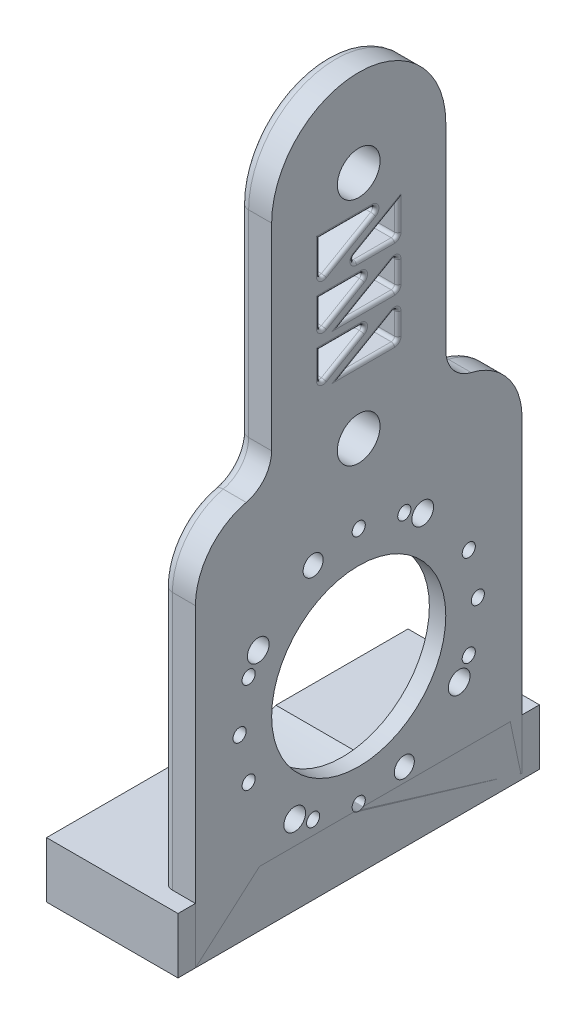
SolidWorks part; units mm, degrees
ref_plane "Front Plane" through (0, 0, 0) normal (0, 0, 1) x (1, 0, 0)
ref_plane "Top Plane" through (0, 0, 0) normal (0, 1, 0) x (1, 0, 0)
ref_plane "Right Plane" through (0, 0, 0) normal (1, 0, 0) x (0, 0, -1)
sketch "Sketch2" plane through (0, 0, 0) normal (1, 0, 0) x (0, 0, -1)
  line L0 (-49.7, 0) -> (-49.7, -54.7)
  line L1 (-49.7, -54.7) -> (49.7, -54.7)
  line L2 (49.7, -54.7) -> (49.7, 30)
  line L3 (0, 0) -> (0, 130) construction
  line L4 (-49.7, 0) -> (-49.7, 130)
  line L6 (49.7, 130) -> (49.7, 30)
  line L7 (-4.0065, 60) -> (3.9935, 60) construction
  line L8 (-49.7, 130) -> (49.7, 130) construction
  arc A0 (-32.0764, 15.2865) -> (-34.9048, 12.4581) centre (-33.4906, 13.8723) ccw
  arc A1 (-34.9048, 12.4581) -> (-32.0764, 15.2865) centre (-33.4906, 13.8723) ccw
  arc A74 (-20.5317, -3.7195) -> (-23.1344, -1.6907) centre (-21.8331, -2.7051) ccw
  arc A75 (-23.1344, -1.6907) -> (-20.5317, -3.7195) centre (-21.8331, -2.7051) ccw
  arc A76 (-16.2541, -14.2736) -> (-18.8568, -12.2448) centre (-17.5554, -13.2592) ccw
  arc A77 (-18.8568, -12.2448) -> (-16.2541, -14.2736) centre (-17.5554, -13.2592) ccw
  arc A78 (-7.2725, -21.275) -> (-9.8752, -19.2461) centre (-8.5738, -20.2605) ccw
  arc A79 (-9.8752, -19.2461) -> (-7.2725, -21.275) centre (-8.5738, -20.2605) ccw
  arc A80 (4.0065, -22.8475) -> (1.4038, -20.8186) centre (2.7051, -21.8331) ccw
  arc A81 (1.4038, -20.8186) -> (4.0065, -22.8475) centre (2.7051, -21.8331) ccw
  arc A82 (14.5606, -18.5698) -> (11.9579, -16.541) centre (13.2592, -17.5554) ccw
  arc A83 (11.9579, -16.541) -> (14.5606, -18.5698) centre (13.2592, -17.5554) ccw
  arc A84 (21.5619, -9.5882) -> (18.9592, -7.5594) centre (20.2605, -8.5738) ccw
  arc A85 (18.9592, -7.5594) -> (21.5619, -9.5882) centre (20.2605, -8.5738) ccw
  arc A86 (23.1344, 1.6907) -> (20.5317, 3.7195) centre (21.8331, 2.7051) ccw
  arc A87 (20.5317, 3.7195) -> (23.1344, 1.6907) centre (21.8331, 2.7051) ccw
  arc A88 (18.8568, 12.2448) -> (16.2541, 14.2736) centre (17.5554, 13.2592) ccw
  arc A89 (16.2541, 14.2736) -> (18.8568, 12.2448) centre (17.5554, 13.2592) ccw
  arc A90 (9.8752, 19.2461) -> (7.2725, 21.275) centre (8.5738, 20.2605) ccw
  arc A91 (7.2725, 21.275) -> (9.8752, 19.2461) centre (8.5738, 20.2605) ccw
  arc A92 (-1.4038, 20.8186) -> (-4.0065, 22.8475) centre (-2.7051, 21.8331) ccw
  arc A93 (-4.0065, 22.8475) -> (-1.4038, 20.8186) centre (-2.7051, 21.8331) ccw
  arc A94 (-11.9579, 16.541) -> (-14.5606, 18.5698) centre (-13.2592, 17.5554) ccw
  arc A95 (-14.5606, 18.5698) -> (-11.9579, 16.541) centre (-13.2592, 17.5554) ccw
  arc A96 (-18.9592, 7.5594) -> (-21.5619, 9.5882) centre (-20.2605, 8.5738) ccw
  arc A97 (-21.5619, 9.5882) -> (-18.9592, 7.5594) centre (-20.2605, 8.5738) ccw
  arc A98 (-17.1437, -28.2395) -> (-21.8106, -32.9064) centre (-19.4771, -30.5729) ccw
  arc A99 (-21.8106, -32.9064) -> (-17.1437, -28.2395) centre (-19.4771, -30.5729) ccw
  arc A102 (32.9064, -17.1437) -> (28.2395, -21.8106) centre (30.5729, -19.4771) ccw
  arc A103 (28.2395, -21.8106) -> (32.9064, -17.1437) centre (30.5729, -19.4771) ccw
  arc A104 (21.8106, 32.9064) -> (17.1437, 28.2395) centre (19.4771, 30.5729) ccw
  arc A105 (17.1437, 28.2395) -> (21.8106, 32.9064) centre (19.4771, 30.5729) ccw
  arc A108 (-28.2395, 21.8106) -> (-32.9064, 17.1437) centre (-30.5729, 19.4771) ccw
  arc A109 (-32.9064, 17.1437) -> (-28.2395, 21.8106) centre (-30.5729, 19.4771) ccw
  arc A110 (-20.9002, 16.2921) -> (20.9002, -16.2921) centre (0, 0) ccw
  arc A111 (20.9002, -16.2921) -> (-20.9002, 16.2921) centre (0, 0) ccw
  circle A112 centre (0, 0) radius 40.5
  arc A113 (16.029, -31.334) -> (11.7156, -35.6473) centre (13.8723, -33.4906) ccw
  arc A114 (-37.6642, -1.4142) -> (-34.8358, 1.4142) centre (-36.25, 0) ccw
  arc A115 (-34.8358, 1.4142) -> (-37.6642, -1.4142) centre (-36.25, 0) ccw
  arc A116 (-34.9048, -15.2865) -> (-32.0764, -12.4581) centre (-33.4906, -13.8723) ccw
  arc A117 (-32.0764, -12.4581) -> (-34.9048, -15.2865) centre (-33.4906, -13.8723) ccw
  arc A118 (-12.4581, -32.0764) -> (-15.2865, -34.9048) centre (-13.8723, -33.4906) ccw
  arc A119 (-15.2865, -34.9048) -> (-12.4581, -32.0764) centre (-13.8723, -33.4906) ccw
  arc A120 (-1.4142, -37.6642) -> (1.4142, -34.8358) centre (0, -36.25) ccw
  arc A121 (1.4142, -34.8358) -> (-1.4142, -37.6642) centre (0, -36.25) ccw
  arc A122 (32.0764, -15.2865) -> (34.9048, -12.4581) centre (33.4906, -13.8723) ccw
  arc A123 (34.9048, -12.4581) -> (32.0764, -15.2865) centre (33.4906, -13.8723) ccw
  arc A124 (34.8358, -1.4142) -> (37.6642, 1.4142) centre (36.25, 0) ccw
  arc A125 (37.6642, 1.4142) -> (34.8358, -1.4142) centre (36.25, 0) ccw
  arc A126 (32.0764, 12.4581) -> (34.9048, 15.2865) centre (33.4906, 13.8723) ccw
  arc A127 (34.9048, 15.2865) -> (32.0764, 12.4581) centre (33.4906, 13.8723) ccw
  arc A128 (15.2865, 34.9048) -> (12.4581, 32.0764) centre (13.8723, 33.4906) ccw
  arc A129 (12.4581, 32.0764) -> (15.2865, 34.9048) centre (13.8723, 33.4906) ccw
  arc A130 (-1.4142, 34.8358) -> (1.4142, 37.6642) centre (0, 36.25) ccw
  arc A131 (1.4142, 37.6642) -> (-1.4142, 34.8358) centre (0, 36.25) ccw
  arc A134 (11.7156, -35.6473) -> (16.029, -31.334) centre (13.8723, -33.4906) ccw
  arc A135 (-16.029, 31.334) -> (-11.7156, 35.6473) centre (-13.8723, 33.4906) ccw
  arc A136 (-11.7156, 35.6473) -> (-16.029, 31.334) centre (-13.8723, 33.4906) ccw
  arc A137 (49.7, 130) -> (-49.7, 130) centre (0, 130) ccw
  circle A138 centre (-0.0065, 60) radius 6.5
  circle A139 centre (0, 130) radius 6.5
  dimension "D1" = 130
  dimension "D2" = 54.7
  dimension "D3" = 70
extrude "Boss-Extrude1" add sketch "Sketch2" along normal blind 5 contours A112 A131 A130 A129 A128 A127 A126 A125 A124 A123 A122 A121 A120 A119 A118 A117 A116 A115 A114 A1 A0 A99 A98 A103 A102 A105 A104 A109 A108 A111 | L4 A112 region at (0, 74.4467, -0.0001) region at (0, 0, 39.3545)
extrude "Boss-Extrude2" add sketch "Sketch2<5>" against normal blind 5 contours L4 A112 region at (0, 74.4467, -0.0001)
sketch "Sketch2<5>" plane through (0, 0, 0) normal (1, 0, 0) x (0, 0, -1) same geometry as "Sketch2"
ref_plane "Plane1" through (0, -54.7, 0) normal (0, -1, 0) x (-1, 0, 0)
sketch "Sketch3" plane through (0, -54.7, 0) normal (0, -1, 0) x (-1, 0, 0)
  line L0 (-5, 0) -> (35, 0) construction
  line L1 (-5, 55) -> (35, 55)
  line L2 (-5, 55) -> (-5, -55)
  line L3 (-5, -55) -> (35, -55)
  line L5 (35, -55) -> (35, 0)
  line L6 (35, 55) -> (35, 0)
  dimension "D1" = 40
  dimension "D2" = 55
extrude "Boss-Extrude3" add sketch "Sketch3" against normal blind 17 separate body
sketch "Sketch7" plane through (5, 0, 0) normal (1, 0, 0) x (0, 0, -1)
  arc A0 (-32.0764, 15.2865) -> (-34.9048, 12.4581) centre (-33.4906, 13.8723) ccw
  arc A1 (-34.9048, 12.4581) -> (-32.0764, 15.2865) centre (-33.4906, 13.8723) ccw
  arc A2 (-20.5317, -3.7195) -> (-23.1344, -1.6907) centre (-21.8331, -2.7051) ccw
  arc A3 (-23.1344, -1.6907) -> (-20.5317, -3.7195) centre (-21.8331, -2.7051) ccw
  arc A4 (-16.2541, -14.2736) -> (-18.8568, -12.2448) centre (-17.5554, -13.2592) ccw
  arc A5 (-18.8568, -12.2448) -> (-16.2541, -14.2736) centre (-17.5554, -13.2592) ccw
  arc A6 (-7.2725, -21.275) -> (-9.8752, -19.2461) centre (-8.5738, -20.2605) ccw
  arc A7 (-9.8752, -19.2461) -> (-7.2725, -21.275) centre (-8.5738, -20.2605) ccw
  arc A8 (4.0065, -22.8475) -> (1.4038, -20.8186) centre (2.7051, -21.8331) ccw
  arc A9 (1.4038, -20.8186) -> (4.0065, -22.8475) centre (2.7051, -21.8331) ccw
  arc A10 (14.5606, -18.5698) -> (11.9579, -16.541) centre (13.2592, -17.5554) ccw
  arc A11 (11.9579, -16.541) -> (14.5606, -18.5698) centre (13.2592, -17.5554) ccw
  arc A12 (21.5619, -9.5882) -> (18.9592, -7.5594) centre (20.2605, -8.5738) ccw
  arc A13 (18.9592, -7.5594) -> (21.5619, -9.5882) centre (20.2605, -8.5738) ccw
  arc A14 (23.1344, 1.6907) -> (20.5317, 3.7195) centre (21.8331, 2.7051) ccw
  arc A15 (20.5317, 3.7195) -> (23.1344, 1.6907) centre (21.8331, 2.7051) ccw
  arc A16 (18.8568, 12.2448) -> (16.2541, 14.2736) centre (17.5554, 13.2592) ccw
  arc A17 (16.2541, 14.2736) -> (18.8568, 12.2448) centre (17.5554, 13.2592) ccw
  arc A18 (9.8752, 19.2461) -> (7.2725, 21.275) centre (8.5738, 20.2605) ccw
  arc A19 (7.2725, 21.275) -> (9.8752, 19.2461) centre (8.5738, 20.2605) ccw
  arc A20 (-1.4038, 20.8186) -> (-4.0065, 22.8475) centre (-2.7051, 21.8331) ccw
  arc A21 (-4.0065, 22.8475) -> (-1.4038, 20.8186) centre (-2.7051, 21.8331) ccw
  arc A22 (-11.9579, 16.541) -> (-14.5606, 18.5698) centre (-13.2592, 17.5554) ccw
  arc A23 (-14.5606, 18.5698) -> (-11.9579, 16.541) centre (-13.2592, 17.5554) ccw
  arc A24 (-18.9592, 7.5594) -> (-21.5619, 9.5882) centre (-20.2605, 8.5738) ccw
  arc A25 (-21.5619, 9.5882) -> (-18.9592, 7.5594) centre (-20.2605, 8.5738) ccw
  arc A26 (-17.1437, -28.2395) -> (-21.8106, -32.9064) centre (-19.4771, -30.5729) ccw
  arc A27 (-21.8106, -32.9064) -> (-17.1437, -28.2395) centre (-19.4771, -30.5729) ccw
  arc A28 (32.9064, -17.1437) -> (28.2395, -21.8106) centre (30.5729, -19.4771) ccw
  arc A29 (28.2395, -21.8106) -> (32.9064, -17.1437) centre (30.5729, -19.4771) ccw
  arc A30 (21.8106, 32.9064) -> (17.1437, 28.2395) centre (19.4771, 30.5729) ccw
  arc A31 (17.1437, 28.2395) -> (21.8106, 32.9064) centre (19.4771, 30.5729) ccw
  arc A32 (-28.2395, 21.8106) -> (-32.9064, 17.1437) centre (-30.5729, 19.4771) ccw
  arc A33 (-32.9064, 17.1437) -> (-28.2395, 21.8106) centre (-30.5729, 19.4771) ccw
  arc A34 (-20.9002, 16.2921) -> (20.9002, -16.2921) centre (0, 0) ccw
  arc A35 (20.9002, -16.2921) -> (-20.9002, 16.2921) centre (0, 0) ccw
  circle A36 centre (0, 0) radius 40.5
  arc A37 (16.029, -31.334) -> (11.7156, -35.6473) centre (13.8723, -33.4906) ccw
  arc A38 (-37.6642, -1.4142) -> (-34.8358, 1.4142) centre (-36.25, 0) ccw
  arc A39 (-34.8358, 1.4142) -> (-37.6642, -1.4142) centre (-36.25, 0) ccw
  arc A40 (-34.9048, -15.2865) -> (-32.0764, -12.4581) centre (-33.4906, -13.8723) ccw
  arc A41 (-32.0764, -12.4581) -> (-34.9048, -15.2865) centre (-33.4906, -13.8723) ccw
  arc A42 (-12.4581, -32.0764) -> (-15.2865, -34.9048) centre (-13.8723, -33.4906) ccw
  arc A43 (-15.2865, -34.9048) -> (-12.4581, -32.0764) centre (-13.8723, -33.4906) ccw
  arc A44 (-1.4142, -37.6642) -> (1.4142, -34.8358) centre (0, -36.25) ccw
  arc A45 (1.4142, -34.8358) -> (-1.4142, -37.6642) centre (0, -36.25) ccw
  arc A46 (32.0764, -15.2865) -> (34.9048, -12.4581) centre (33.4906, -13.8723) ccw
  arc A47 (34.9048, -12.4581) -> (32.0764, -15.2865) centre (33.4906, -13.8723) ccw
  arc A48 (34.8358, -1.4142) -> (37.6642, 1.4142) centre (36.25, 0) ccw
  arc A49 (37.6642, 1.4142) -> (34.8358, -1.4142) centre (36.25, 0) ccw
  arc A50 (32.0764, 12.4581) -> (34.9048, 15.2865) centre (33.4906, 13.8723) ccw
  arc A51 (34.9048, 15.2865) -> (32.0764, 12.4581) centre (33.4906, 13.8723) ccw
  arc A52 (15.2865, 34.9048) -> (12.4581, 32.0764) centre (13.8723, 33.4906) ccw
  arc A53 (12.4581, 32.0764) -> (15.2865, 34.9048) centre (13.8723, 33.4906) ccw
  arc A54 (-1.4142, 34.8358) -> (1.4142, 37.6642) centre (0, 36.25) ccw
  arc A55 (1.4142, 37.6642) -> (-1.4142, 34.8358) centre (0, 36.25) ccw
  arc A56 (35.1432, 35.1432) -> (-35.1432, -35.1432) centre (0, 0) ccw
  arc A57 (-35.1432, -35.1432) -> (35.1432, 35.1432) centre (0, 0) ccw
  arc A58 (11.7156, -35.6473) -> (16.029, -31.334) centre (13.8723, -33.4906) ccw
  arc A59 (-16.029, 31.334) -> (-11.7156, 35.6473) centre (-13.8723, 33.4906) ccw
  arc A60 (-11.7156, 35.6473) -> (-16.029, 31.334) centre (-13.8723, 33.4906) ccw
  circle M7 centre (13.8723, -33.4906) radius 3.05
  circle M13 centre (0, -36.25) radius 2
  circle M14 centre (-13.8723, -33.4906) radius 2
  circle M18 centre (-19.4771, -30.5729) radius 3.3
extrude "Cut-Extrude8" cut sketch "Sketch2<11>" against normal blind 50 contours A112 A136 A135 A134 A113 A131 A130 A129 A128 A127 A126 A125 A124 A123 A122 A121 A120 A119 A118 A117 A116 A115 A114 A1 A0 A99 A98 A103 A102 A105 A104 A109 A108 A111 region at (0, 0, 39.3545)
sketch "Sketch2<11>" plane through (0, 0, 0) normal (1, 0, 0) x (0, 0, -1) same geometry as "Sketch2"
extrude "Cut-Extrude9" cut sketch "Sketch7" against normal through all contours M13 | M7 | M14 | M18 | A37 A58 region at (5, -30.5729, 19.4771) region at (5, -33.4906, -13.8723) region at (5, -33.4906, 13.8723) region at (5, -36.25, 0)
sketch "Sketch8" plane through (5, 0, 0) normal (1, 0, 0) x (0, 0, -1)
  line L0 (-0.0065, 60) -> (49.7, 60) construction
  line L1 (26.5, 130) -> (26.5, 60) construction
  line L2 (0, 130) -> (-0.0065, 60) construction
  line L3 (49.7, -54.7) -> (49.7, 130)
  line L4 (-49.7, 130) -> (-49.7, -54.7)
  line L5 (-49.7, -54.7) -> (49.7, -54.7)
  line L6 (49.7, -54.7) -> (49.7, 130)
  line L7 (-49.7, 130) -> (-49.7, -54.7)
  line L8 (-49.7, -54.7) -> (49.7, -54.7)
  line L9 (26.5, 130) -> (26.5, 60)
  line L10 (26.5, 60) -> (49.7, 60)
  line L11 (-26.5129, 60.0049) -> (-49.7129, 60.0092)
  line L12 (-26.5, 130.0049) -> (-26.5129, 60.0049)
  circle A0 centre (-0.0065, 60) radius 6.5 construction
  arc A1 (49.7, 130) -> (-49.7, 130) centre (0, 130) ccw
  arc A2 (49.7, 130) -> (-49.7, 130) centre (0, 130) ccw
  circle A3 centre (0, 130) radius 6.5 construction
  circle A4 centre (-0.0065, 60) radius 6.5
  circle A5 centre (0, 130) radius 6.5
  arc A6 (26.5, 130) -> (-26.5, 130.0049) centre (0, 130) ccw
  circle A7 centre (0, 130) radius 26.5 construction
  arc M31 (49.7, 130) -> (-49.7, 130) centre (0, 130) ccw
  line M32 (-49.7, 130) -> (-49.7, -54.7)
  dimension "D1" = 0
  dimension "D2" = 20
extrude "Cut-Extrude10" cut sketch "Sketch8" against normal blind 10 contours A6 L9 L10 L6 L11 L12 M31 M32 region at (5, 61.5559, -38.1)
fillet "Fillet1" radius 10 2 edges at (0, 60.0049, 26.5129) (0, 60, -26.5)
fillet "Fillet2" radius 20 2 edges at (0, 60.0092, 49.7) (0, 60, -49.7)
fillet "Fillet3" radius 1 1 edges at (-5, 0, -40.5)
fillet "Fillet4" radius 3 9 edges at (-5, -6.9596, -49.7) (-5, 53.2173, -45.3631) (-5, 63.7817, -28.6684) (-5, 100, -26.5) (-5, -6.9549, 49.7) (-5, 53.2237, 45.3655) (-5, 63.7892, 28.6789) (-5, 100.0049, 26.5055) (-5, 156.5, -0.0024)
sketch "Sketch9" plane through (-5, 0, 0) normal (-1, 0, 0) x (0, 0, 1)
  line L0 (0, 130) -> (0, 118.6831) construction
  line L1 (-11.8762, 118.6831) -> (11.8762, 118.6831)
  line L2 (-11.8762, 118.6831) -> (-11.8762, 71.3169)
  line L3 (-11.8762, 71.3169) -> (11.8762, 71.3169)
  line L4 (11.8762, 118.6831) -> (11.8762, 71.3169)
  line L5 (-11.8762, 118.6831) -> (11.8762, 104.9696)
  line L6 (11.8762, 104.9696) -> (-11.8762, 104.9696)
  line L7 (-11.8762, 104.9696) -> (11.8762, 91.2562)
  line L8 (11.8762, 91.2562) -> (-11.8762, 91.2562)
  line L9 (-11.8762, 91.2562) -> (11.8762, 77.5427)
  line L10 (11.8762, 77.5427) -> (-11.8762, 77.5427)
  line L11 (-11.8762, 77.5427) -> (-0.0004, 70.6861)
  line L12 (-11.8762, 116.3737) -> (4.4121, 106.9696)
  line L13 (4.4121, 106.9696) -> (-11.8762, 106.9696)
  line L14 (-11.8762, 102.6602) -> (4.4121, 93.2562)
  line L15 (4.4121, 93.2562) -> (-11.8762, 93.2562)
  line L16 (-11.8762, 88.9468) -> (4.4121, 79.5427)
  line L17 (4.4121, 79.5427) -> (-11.8762, 79.5427)
  line L18 (-11.8762, 75.2333) -> (-5.0928, 71.3169)
  line L19 (-7.8762, 118.6831) -> (11.8762, 107.279)
  line L20 (11.8762, 102.9696) -> (-4.4121, 102.9696)
  line L21 (-4.4121, 102.9696) -> (11.8762, 93.5656)
  line L22 (11.8762, 89.2562) -> (-4.4121, 89.2562)
  line L23 (-4.4121, 89.2562) -> (11.8762, 79.8521)
  line L24 (11.8762, 75.5427) -> (-4.4121, 75.5427)
  line L25 (-4.4121, 75.5427) -> (2.9072, 71.3169)
  line L26 (-0.0004, 70.6861) -> (0, 71.3169) construction
  point P0 (8.8533, 91.3721)
  point P37 (0, 130)
extrude "Cut-Extrude11" cut sketch "Sketch9" against normal blind 10 contours L13 L12 L2 | L1 L19 L4 | L20 L21 L4 | L22 L23 L4 | L15 L14 L2 | L17 L16 L2 region at (-5, 114.8818, 5.2921) region at (-5, 110.1043, -6.4468) region at (-5, 99.8349, 6.4468) region at (-5, 96.3909, -6.4468) region at (-5, 86.1215, 6.4468) region at (-5, 82.6774, -6.4468)
fillet "Fillet5" radius 1 48 edges at (5, 118.6831, 2) (-5, 118.6831, 2) (5, 112.9811, 11.8762) (-5, 112.9811, 11.8762) (5, 111.6717, -11.8762) (-5, 111.6717, -11.8762) (5, 111.6717, -3.7321) (-5, 111.6717, -3.7321) (5, 102.9696, 3.7321) (-5, 102.9696, 3.7321) (5, 98.2676, 11.8762) (-5, 98.2676, 11.8762) (5, 89.2562, 3.7321) (-5, 89.2562, 3.7321) (5, 84.5541, 11.8762) (-5, 84.5541, 11.8762) (5, 97.9582, -3.7321) (-5, 97.9582, -3.7321) (5, 93.2562, -3.7321) (-5, 93.2562, -3.7321) (5, 84.2447, -3.7321) (-5, 84.2447, -3.7321) (5, 79.5427, -3.7321) (-5, 79.5427, -3.7321) (0, 118.6831, -7.8762) (5, 112.9811, 2) (0, 107.279, 11.8762) (-5, 112.9811, 2) (0, 106.9696, -11.8762) (5, 106.9696, -3.7321) (0, 106.9696, 4.4121) (-5, 106.9696, -3.7321) (0, 102.9696, -4.4121) (5, 98.2676, 3.7321) (0, 93.5656, 11.8762) (-5, 98.2676, 3.7321) (0, 89.2562, -4.4121) (5, 84.5541, 3.7321) (0, 79.8521, 11.8762) (-5, 84.5541, 3.7321) (0, 102.6602, -11.8762) (5, 97.9582, -11.8762) (0, 93.2562, -11.8762) (-5, 97.9582, -11.8762) (0, 88.9468, -11.8762) (5, 84.2447, -11.8762) (0, 79.5427, -11.8762) (-5, 84.2447, -11.8762)
